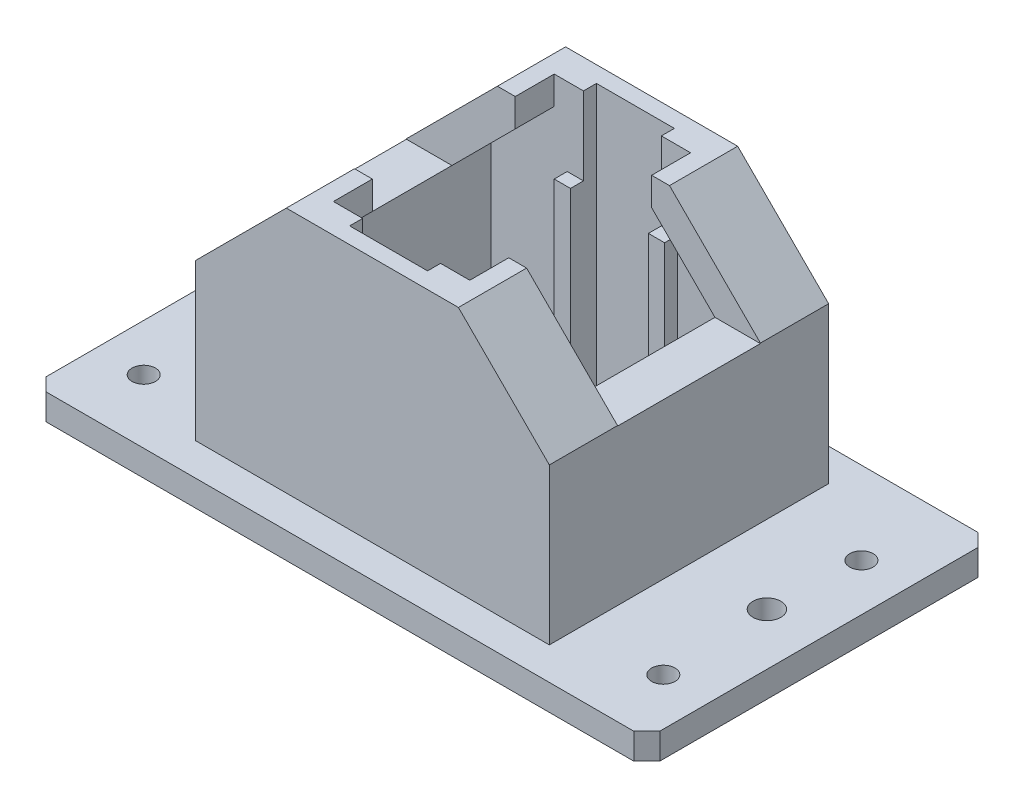
SolidWorks part; units mm, degrees
ref_plane "Płaszczyzna przednia" through (0, 0, 0) normal (0, 0, 1) x (1, 0, 0)
ref_plane "Płaszczyzna górna" through (0, 0, 0) normal (0, 1, 0) x (1, 0, 0)
ref_plane "Płaszczyzna prawa" through (0, 0, 0) normal (1, 0, 0) x (0, 0, -1)
sketch "Sketch1" plane through (0, 0, 0) normal (0, 1, 0) x (1, 0, 0)
  line L0 (0, 19.4294) -> (0, -20.6549) construction
  line L1 (-20.25, 17) -> (20.25, 17)
  line L2 (-20.25, 17) -> (-20.25, -17)
  line L3 (-20.25, -17) -> (20.25, -17)
  line L4 (20.25, 17) -> (20.25, -17)
  line L5 (-20.25, 17) -> (20.25, -17) construction
  line L6 (-20.25, -17) -> (20.25, 17) construction
  line L7 (-32.8665, 0) -> (32.8665, 0) construction
  line L8 (8.5, 15) -> (6, 15)
  line L9 (-8.5, 17) -> (-6, 17)
  line L10 (-8.5, 17) -> (-8.5, 15)
  line L11 (-8.5, 15) -> (-6, 15)
  line L12 (-6, 17) -> (-6, 15)
  line L13 (6, 17) -> (6, 15)
  line L14 (8.5, 17) -> (6, 17)
  line L15 (8.5, 17) -> (8.5, 15)
  line L16 (8.5, -17) -> (8.5, -15)
  line L17 (8.5, -17) -> (6, -17)
  line L18 (6, -17) -> (6, -15)
  line L19 (8.5, -15) -> (6, -15)
  line L20 (-8.5, -15) -> (-6, -15)
  line L21 (-6, -17) -> (-6, -15)
  line L22 (-8.5, -17) -> (-6, -17)
  line L23 (-8.5, -17) -> (-8.5, -15)
  line L24 (-27.25, 24) -> (-27.25, -24)
  line L25 (-27.25, -24) -> (27.25, -24)
  line L26 (27.25, 24) -> (27.25, -24)
  line L27 (-27.25, 24) -> (27.25, 24)
  point P0 (0, 0)
  point P10 (0, 17)
  dimension "D1" = 34
  dimension "D2" = 40.5
  dimension "D3" = 2.5
  dimension "D4" = 2
  dimension "D5" = 6
  dimension "1" = 7
extrude "Boss-Extrude1" add sketch "Sketch1" along normal blind 42 contours L15 L1 L13 L8 | L27 L24 L25 L26 L22 L23 L3 L2 L1 L4 L21 | L11 L12 L9 L10 | L20 L21 L22 L23 | L19 L18 L17 L16 region at (7.25, 0, -16) region at (0, 0, -23.2738)
chamfer "Chamfer2" distance 14 angle 45 2 edges at (27.25, 42, 0) (-27.25, 42, 0)
chamfer "Chamfer3" distance 10 angle 45 2 edges at (20.25, 35, 0) (-20.25, 35, 0) first distance on face at (18.5, 36.75, 0) first distance on face at (-18.5, 36.75, 0)
sketch "Sketch2" plane through (0, 0, -17) normal (0, 0, 1) x (1, 0, 0)
  line L1 (-27.25, 20.9289) -> (-6.1789, 42)
  line L3 (-27.25, 28) -> (-27.25, 27.9289) construction
  line L8 (0, 51.2829) -> (0, -13.1032) construction
  line L9 (-6, 42) -> (6, 42) construction
  line L12 (-27.25, 28) -> (-13.25, 42)
  line L13 (-13.25, 42) -> (-6.1789, 42)
  line L14 (-13.25, 42) -> (-27.25, 28) construction
  line L15 (-27.25, 28) -> (-27.25, 20.9289)
  line L16 (13.25, 42) -> (6.1789, 42)
  line L17 (27.25, 28) -> (13.25, 42)
  line L18 (27.25, 28) -> (27.25, 20.9289)
  line L19 (27.25, 20.9289) -> (6.1789, 42)
  dimension "D1" = 5
extrude "Boss-Extrude2" add sketch "Sketch2" along normal blind 6
ref_plane "Plane1" through (0, 0, 0) normal (0, 0, 1) x (1, 0, 0)
mirror "Mirror2" about plane through (0, 0, 0) normal (0, 0, 1) of "Boss-Extrude2"
sketch "Sketch4" plane through (0, 0, 0) normal (0, -1, 0) x (1, 0, 0)
  line L0 (0, 30.4744) -> (0, -31.4814) construction
  line L1 (27.25, 24) -> (47.25, 24)
  line L2 (27.25, 24) -> (27.25, -24)
  line L3 (27.25, -24) -> (47.25, -24)
  line L4 (47.25, 24) -> (47.25, -24)
  line L5 (-27.25, -24) -> (-47.25, -24)
  line L6 (-47.25, 24) -> (-47.25, -24)
  line L7 (-27.25, 24) -> (-47.25, 24)
  line L8 (-27.25, 24) -> (-27.25, -24)
  line L9 (-55.8577, 0) -> (55.4548, 0) construction
  dimension "D1" = 20
extrude "Boss-Extrude3" add sketch "Sketch4" against normal blind 4
sketch "Sketch5" plane through (0, 42, 0) normal (0, 1, 0) x (1, 0, 0)
  line L0 (0, 26.9268) -> (0, -17) construction
  line L1 (-10.5, 17) -> (10.5, 17)
  line L2 (-10.5, 17) -> (-10.5, -17)
  line L3 (-10.5, -17) -> (10.5, -17)
  line L4 (10.5, 17) -> (10.5, -17)
  line L7 (20.25, -17) -> (8.5, -17) construction
  line L8 (-6, 17) -> (6, 17) construction
  dimension "D1" = 21
extrude "Cut-Extrude1" cut sketch "Sketch5" against normal blind 12
sketch "Sketch6" plane through (0, 0, 17) normal (0, 0, -1) x (-1, 0, 0)
  line L0 (10.5, 42) -> (-10.5, 42) construction
  line L1 (-6, 42) -> (6, 42)
  line L2 (-6, 42) -> (-6, 0)
  line L3 (-6, 0) -> (6, 0)
  line L4 (6, 42) -> (6, 0)
extrude "Cut-Extrude2" cut sketch "Sketch6" against normal blind 2
mirror "Mirror3" about plane through (0, 0, 0) normal (0, 0, 1) of "Cut-Extrude2"
sketch "Sketch7" plane through (0, 0, -24) normal (0, 0, -1) x (-1, 0, 0)
  line L10 (13.25, 42) -> (-13.25, 42)
  line L11 (-13.25, 42) -> (-27.25, 28)
  line L12 (-27.25, 28) -> (-27.25, 4)
  line L13 (-27.25, 4) -> (-47.25, 4)
  line L14 (-47.25, 4) -> (-47.25, 0)
  line L15 (-47.25, 0) -> (47.25, 0)
  line L16 (47.25, 0) -> (47.25, 4)
  line L17 (47.25, 4) -> (27.25, 4)
  line L18 (27.25, 4) -> (27.25, 28)
  line L19 (27.25, 28) -> (13.25, 42)
  line L20 (13.25, 42) -> (-13.25, 42)
  line L21 (-13.25, 42) -> (-27.25, 28)
  line L22 (-27.25, 28) -> (-27.25, 4)
  line L23 (-27.25, 4) -> (-47.25, 4)
  line L24 (-47.25, 4) -> (-47.25, 0)
  line L25 (-47.25, 0) -> (47.25, 0)
  line L26 (47.25, 0) -> (47.25, 4)
  line L27 (47.25, 4) -> (27.25, 4)
  line L28 (27.25, 4) -> (27.25, 28)
  line L29 (27.25, 28) -> (13.25, 42)
  dimension "D1" = 0
extrude "Cut-Extrude3" cut sketch "Sketch7" against normal blind 2.5
sketch "Sketch8" plane through (0, 0, 24) normal (0, 0, 1) x (1, 0, 0)
  line L10 (27.25, 4) -> (27.25, 28)
  line L11 (27.25, 28) -> (13.25, 42)
  line L12 (13.25, 42) -> (-13.25, 42)
  line L13 (-13.25, 42) -> (-27.25, 28)
  line L14 (-27.25, 28) -> (-27.25, 4)
  line L15 (-27.25, 4) -> (-47.25, 4)
  line L16 (-47.25, 4) -> (-47.25, 0)
  line L17 (-47.25, 0) -> (47.25, 0)
  line L18 (47.25, 0) -> (47.25, 4)
  line L19 (47.25, 4) -> (27.25, 4)
  line L20 (27.25, 4) -> (27.25, 28)
  line L21 (27.25, 28) -> (13.25, 42)
  line L22 (13.25, 42) -> (-13.25, 42)
  line L23 (-13.25, 42) -> (-27.25, 28)
  line L24 (-27.25, 28) -> (-27.25, 4)
  line L25 (-27.25, 4) -> (-47.25, 4)
  line L26 (-47.25, 4) -> (-47.25, 0)
  line L27 (-47.25, 0) -> (47.25, 0)
  line L28 (47.25, 0) -> (47.25, 4)
  line L29 (47.25, 4) -> (27.25, 4)
  dimension "D1" = 0
extrude "Cut-Extrude4" cut sketch "Sketch8" against normal blind 2.5
sketch "Sketch11" plane through (0, 0, 0) normal (0, -1, 0) x (-1, 0, 0)
  point P0 (-40, 13.8)
  point P3 (-40, -16.7)
  point P6 (40, 13.8)
  point P9 (40, -16.7)
hole_wizard "M3 Clearance Hole1" positions "Sketch11" profile "Sketch10" hole size "M3" standard "DIN"
sketch "Sketch10" plane through (40, 0, -13.8) normal (1, 0, 0) x (0, 0, -1)
  line L0 (0, 0) -> (0, 11.0815)
  line L1 (0, 11.0815) -> (1.8, 10)
  line L2 (1.8, 10) -> (1.8, 0)
  line L5 (1.8, 0) -> (0, 0)
  line L10 (0, 11.0815) -> (-1.8, 10) construction
  line L11 (0, -6.35) -> (0, 107.95) construction
  dimension "Hole Dia." = 3.6
  dimension "Hole Depth" = 10
  dimension "Drill Angle" = 118
sketch "Sketch12" plane through (0, 0, 0) normal (0, -1, 0) x (1, 0, 0)
  line L1 (-47.25, 21.5) -> (47.25, 21.5)
  line L2 (-47.25, 21.5) -> (-47.25, 26.5)
  line L3 (-47.25, 26.5) -> (47.25, 26.5)
  line L4 (47.25, 21.5) -> (47.25, 26.5)
  line L5 (47.25, -21.5) -> (-47.25, -21.5)
  line L6 (47.25, -21.5) -> (47.25, -26.5)
  line L7 (47.25, -26.5) -> (-47.25, -26.5)
  line L8 (-47.25, -21.5) -> (-47.25, -26.5)
  dimension "D1" = 5
extrude "Boss-Extrude4" add sketch "Sketch12" against normal up to surface (4 mm away) up to face at (-40, 4, -12)
chamfer "Chamfer4" distance 2 angle 45 4 edges at (-47.25, 2, -26.5) (47.25, 2, -26.5) (47.25, 2, 26.5) (-47.25, 2, 26.5)
sketch "Sketch15" plane through (0, 4, 0) normal (0, 1, 0) x (1, 0, 0)
  line L0 (-47.25, 0) -> (47.25, 0) construction
  line L1 (-47.25, -24.5) -> (-47.25, 24.5) construction
  line L2 (47.25, 24.5) -> (47.25, -24.5) construction
  point P8 (-39.25, 0)
  point P10 (39.25, 0)
  dimension "D1" = 8
  dimension "D2" = 8
hole_wizard "Ø4.3 (4.3) Diameter Hole1" positions "Sketch15" profile "Sketch14" hole size "Ø4.3" standard "DIN" end condition through all
sketch "Sketch14" plane through (39.25, 4, 0) normal (1, 0, 0) x (0, 0, 1)
  line L0 (0, 0) -> (0, 4)
  line L1 (0, 4) -> (2.15, 4)
  line L2 (2.15, 4) -> (2.15, 0)
  line L5 (2.15, 0) -> (0, 0)
  line L11 (0, -6.35) -> (0, 107.95) construction
  dimension "Thru Hole Dia." = 4.3
  dimension "Thru Hole Depth" = 4
